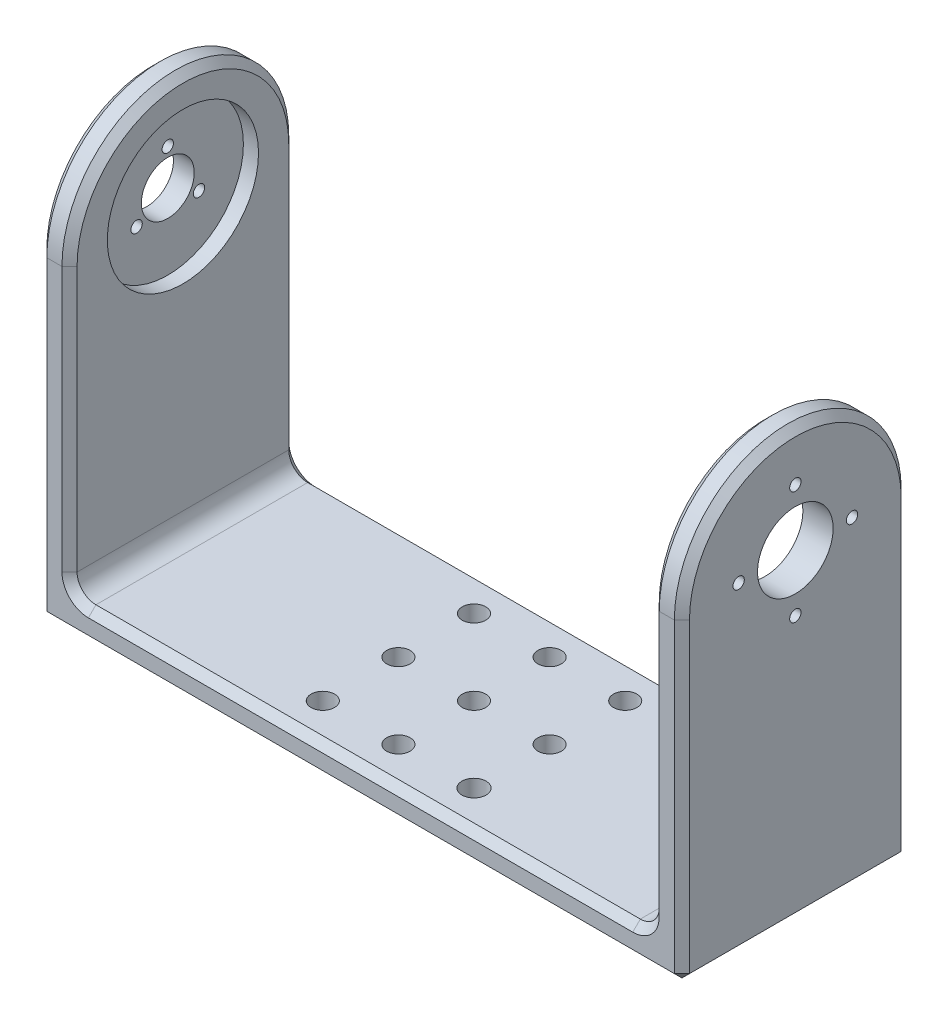
SolidWorks part; units mm, degrees
ref_plane "Front Plane" through (0, 0, 0) normal (0, 0, 1) x (1, 0, 0)
ref_plane "Top Plane" through (0, 0, 0) normal (0, 1, 0) x (1, 0, 0)
ref_plane "Right Plane" through (0, 0, 0) normal (1, 0, 0) x (0, 0, -1)
sketch "Sketch1" plane through (0, 0, 0) normal (0, 1, 0) x (1, 0, 0)
  line L1 (-85, 30) -> (85, 30)
  line L2 (-85, 30) -> (-85, -30)
  line L3 (-85, -30) -> (85, -30)
  line L4 (85, 30) -> (85, -30)
extrude "Boss-Extrude1" add sketch "Sketch1" along normal blind 8
sketch "Sketch2" plane through (0, 8, 0) normal (0, 1, 0) x (1, 0, 0)
  line L1 (-85, 30) -> (-77, 30)
  line L2 (-85, 30) -> (-85, -30)
  line L3 (-85, -30) -> (-77, -30)
  line L4 (-77, 30) -> (-77, -30)
  line L5 (77, 30) -> (77, -30)
  line L6 (85, -30) -> (77, -30)
  line L7 (85, 30) -> (85, -30)
  line L8 (85, 30) -> (77, 30)
extrude "Boss-Extrude2" add sketch "Sketch2" along normal blind 105
sketch "Sketch3" plane through (85, 0, 0) normal (1, 0, 0) x (0, 0, -1)
  circle A0 centre (0, 85) radius 10
  circle A3 centre (0, 70) radius 1.5
  circle A4 centre (0, 100) radius 1.5
  circle A5 centre (-15, 85) radius 1.5
  circle A6 centre (15, 85) radius 1.5
extrude "Cut-Extrude1" cut sketch "Sketch3" against normal blind 10
sketch "Sketch5" plane through (-85, 0, 0) normal (-1, 0, 0) x (0, 0, 1)
  circle A0 centre (0, 85) radius 17
extrude "Boss-Extrude3" add sketch "Sketch5" along normal blind 1.5
sketch "Sketch6" plane through (-86.5, 0, 0) normal (-1, 0, 0) x (0, 0, 1)
  circle A0 centre (0, 85) radius 7
extrude "Cut-Extrude3" cut sketch "Sketch6" against normal blind 15
sketch "Sketch7" plane through (-77, 0, 0) normal (1, 0, 0) x (0, 0, -1)
  circle A0 centre (0, 85) radius 20
extrude "Cut-Extrude4" cut sketch "Sketch7" against normal blind 4
fillet "Fillet1" 2 edges at (81, 113, -30) (81, 113, 30) type full round first side face at (0, 58.5, -30) second side face at (0, 58.5, 30) middle face at (81, 113, 0)
fillet "Fillet2" 2 edges at (-81, 113, -30) (-81, 113, 30) type full round first side face at (0, 51, -30) second side face at (0, 51, 30) middle face at (-81, 113, 0)
fillet "Fillet3" radius 5 1 edges at (77, 8, 0) type face fillet first side face at (77, 70, -1.5) second side face at (0, 8, 0)
fillet "Fillet4" radius 5 1 edges at (-77, 8, 0) type face fillet first side face at (-77, 85, -20) second side face at (-2.5, 8, 0)
fillet "Chamfer1" radius 2 22 edges at (85, 113, 0) (77, 113, 0) (-77, 113, 0) (-85, 113, 0) (85, 41.5, -30) (77, 48, -30) (75.5355, 9.4645, -30) (0, 8, -30) (-75.5355, 9.4645, -30) (-77, 48, -30) (-85, 41.5, -30) (-77, 48, 30) (-75.5355, 9.4645, 30) (0, 8, 30) (75.5355, 9.4645, 30) (77, 48, 30) (85, 41.5, 30) (-85, 41.5, 30) (0, 0, -30) (0, 0, 30) (85, 0, 0) (-85, 0, 0) profile chamfer
sketch "Sketch8" plane through (0, 8, 0) normal (0, 1, 0) x (1, 0, 0)
  circle A0 centre (0, 0) radius 3.1
  circle A1 centre (0, 20) radius 3.1
  circle A2 centre (0, -20) radius 3.1
  circle A3 centre (-20, -20) radius 3.1
  circle A4 centre (-20, 20) radius 3.1
  circle A5 centre (-20, 0) radius 3.1
  circle A6 centre (20, -20) radius 3.2
  circle A7 centre (20, 0) radius 3.1
  circle A8 centre (20, 20) radius 3.1
extrude "Cut-Extrude5" cut sketch "Sketch8" against normal blind 10
sketch "Sketch10" plane through (-81, 0, 0) normal (1, 0, 0) x (0, 0, -1)
  circle A1 centre (0, 94.525) radius 1.5
  circle A2 centre (8.2489, 80.2375) radius 1.5
  circle A3 centre (-8.2489, 80.2375) radius 1.5
  point P10 (0, 85)
  dimension "D1" = 3
extrude "Cut-Extrude7" cut sketch "Sketch10" against normal blind 10
chamfer "Chamfer2" distance 1 angle 45 1 edges at (-85, 85, -17)
